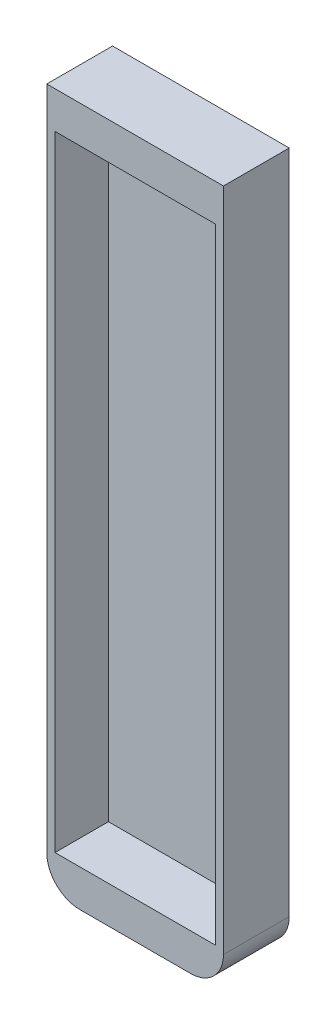
SolidWorks part; units mm, degrees
ref_plane "Спереди" through (0, 0, 0) normal (0, 0, 1) x (1, 0, 0)
ref_plane "Сверху" through (0, 0, 0) normal (0, 1, 0) x (1, 0, 0)
ref_plane "Справа" through (0, 0, 0) normal (1, 0, 0) x (0, 0, -1)
sketch "Эскиз1" plane through (0, 0, 0) normal (0, 0, 1) x (1, 0, 0)
  line L1 (0, 0) -> (43, 0)
  line L2 (0, 0) -> (0, 170)
  line L3 (0, 170) -> (43, 170)
  line L4 (43, 0) -> (43, 170)
  dimension "D1" = 43
  dimension "D2" = 170
extrude "Бобышка-Вытянуть1" add sketch "Эскиз1" along normal blind 16
sketch "Эскиз3" plane through (0, 0, 16) normal (0, 0, 1) x (1, 0, 0)
  line L0 (21.5, 0) -> (21.5, 170) construction
  line L1 (0, 0) -> (43, 0) construction
  line L2 (43, 170) -> (0, 170) construction
  line L4 (2, 161) -> (41, 161)
  line L5 (2, 161) -> (2, 9)
  line L6 (2, 9) -> (41, 9)
  line L7 (41, 161) -> (41, 9)
  line L8 (2, 161) -> (41, 9) construction
  line L9 (2, 9) -> (41, 161) construction
  point P6 (21.5, 85)
  dimension "D1" = 39
  dimension "D2" = 152
extrude "Вырез-Вытянуть1" cut sketch "Эскиз3" against normal blind 13
fillet "Скругление3" radius 8 2 edges at (43, 0, 8) (0, 0, 8)
